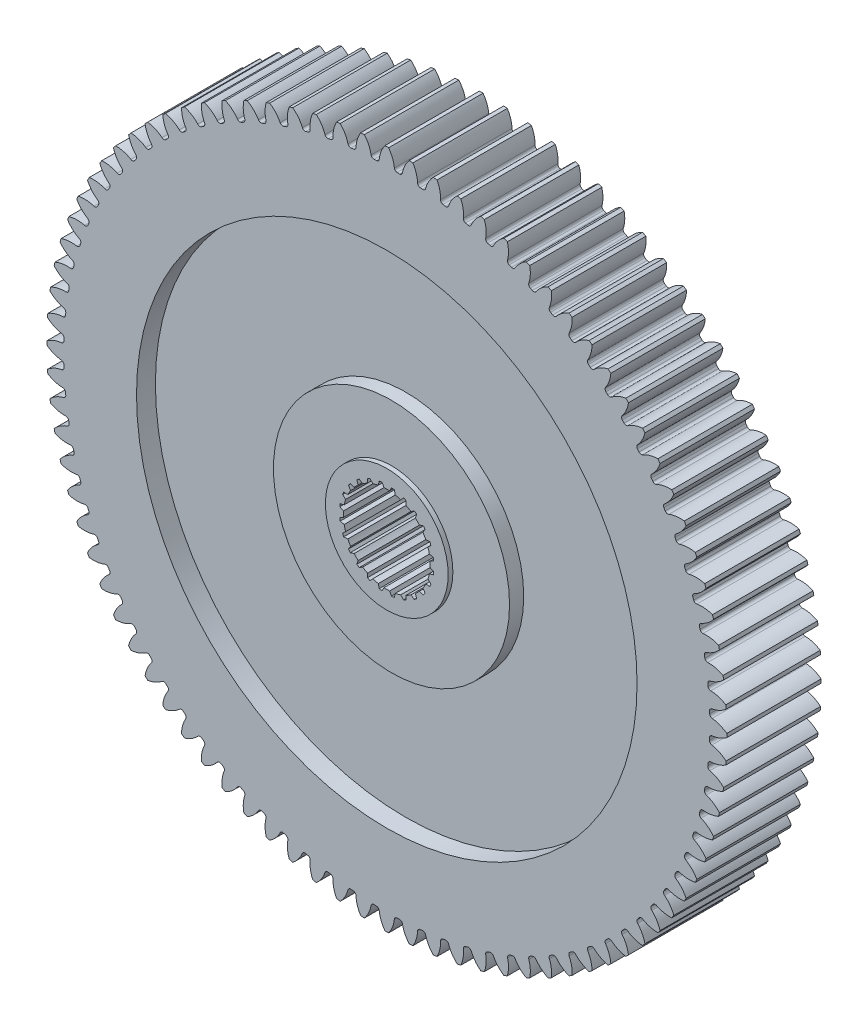
SolidWorks part; units mm, degrees
material "Acier allié"
ref_plane "Plan de face" through (0, 0, 0) normal (0, 0, 1) x (1, 0, 0)
ref_plane "Plan de dessus" through (0, 0, 0) normal (0, 1, 0) x (1, 0, 0)
ref_plane "Plan de droite" through (0, 0, 0) normal (1, 0, 0) x (0, 0, -1)
ref_axis "Axe roue" through (0, 0, 0) along (0, 0, 1)
sketch "Esquisse1" plane through (0, 0, 0) normal (1, 0, 0) x (0, 0, -1)
  line L0 (-15.5122, 0) -> (15.5122, 0) construction
  line L1 (0, 0) -> (0, 36) construction
  line L2 (-5, 4.6) -> (5, 4.6)
  line L3 (-5, 4.6) -> (-5, 6.5)
  line L4 (-5, 36) -> (5, 36)
  line L5 (5, 4.6) -> (5, 6.5)
  line L6 (-5, 26.5) -> (-3, 26.5)
  line L7 (-3, 26.5) -> (-3, 12.5)
  line L8 (-4.5, 6.5) -> (-5, 6.5)
  line L9 (-5, 26.5) -> (-5, 36)
  line L10 (4.5, 6.5) -> (5, 6.5)
  line L11 (3, 26.5) -> (3, 12.5)
  line L12 (5, 26.5) -> (3, 26.5)
  line L13 (5, 26.5) -> (5, 36)
  line L14 (4.5, 6.5) -> (4.5, 12.5)
  line L15 (4.5, 12.5) -> (3, 12.5)
  line L16 (-3, 12.5) -> (-4.5, 12.5)
  line L17 (-4.5, 12.5) -> (-4.5, 6.5)
  dimension "D1" = 9.2
  dimension "D2" = 72
  dimension "D3" = 10
  dimension "D4" = 2
  dimension "D5" = 53
  dimension "D6" = 13
  dimension "D7" = 25
  dimension "D8" = 1.5
revolve "Révolution1" add sketch "Esquisse1" angle 360 about L0
sketch "Esquisse2" plane through (0, 0, 0) normal (0, 0, 1) x (1, 0, 0)
  line L2 (0, -5.5) -> (0, 5.5) construction
  line L4 (0.25, 4.4931) -> (0.5, 4.9749)
  line L6 (0, 0) -> (0, 5.7732) construction
  line L7 (0, 0) -> (0.8204, 6.2318) construction
  line L8 (0.9214, 4.4047) -> (0.8046, 4.9348)
  arc A4 (0.9214, 4.4047) -> (0.25, 4.4931) centre (0, 0) ccw
  arc A5 (0.8046, 4.9348) -> (0.5, 4.9749) centre (0, 0) ccw
  dimension "D1" = 9
  dimension "D5" = 10
  dimension "D2" = 7.5
  dimension "D3" = 0.5
  dimension "D4" = 1
extrude "Enlèv. mat.-Extru.1" cut sketch "Esquisse2" against normal through all and the other way through all
pattern_circular "Répétition circulaire1" count 24 over 360 about axis through (0, 0, 0) along (0, 0, 1) of "Enlèv. mat.-Extru.1"
sketch "Esquisse3" plane through (0, 0, 0) normal (0, 0, 1) x (1, 0, 0)
  line L0 (0, 0) -> (0, 36) construction
  line L1 (0, 0) -> (2.5682, 35.9083) construction
  line L2 (0, 0) -> (1.2849, 35.9771) construction
  line L3 (0.6283, 35.1944) -> (0.3356, 35.9984) construction
  arc A0 (1.3506, 34.1733) -> (1.0907, 34.1826) centre (0, 0) ccw
  arc A1 (0.1965, 35.9995) -> (0.8021, 34.4497) centre (-2.3787, 34.0999) cw
  circle A2 centre (0, 0) radius 35.2 construction
  arc A3 (0.1965, 35.9995) -> (2.3722, 35.9218) centre (0, 0) cw
  circle A4 centre (0, 0) radius 36 construction
  circle A5 centre (0.6283, 35.1944) radius 0.6283 construction
  arc A6 (0.8021, 34.4497) -> (1.0907, 34.1826) centre (1.1003, 34.4824) ccw
  arc A7 (1.6576, 34.4191) -> (1.3506, 34.1733) centre (1.3625, 34.4731) cw
  arc A8 (2.3722, 35.9218) -> (1.6576, 34.4191) centre (4.8053, 33.8433) ccw
  point P9 (0.6283, 35.1944)
  dimension "D2" = 68.4
  dimension "D3" = 70.4
  dimension "D4" = 0.3
  dimension "D6" = 3.2
  dimension "D1" = 4.091
  dimension "D5" = 20
extrude "Enlèv. mat.-Extru.2" cut sketch "Esquisse3" against normal through all and the other way through all
pattern_circular "Répétition circulaire2" count 88 over 360 about axis through (0, 0, 0) along (0, 0, 1) of "Enlèv. mat.-Extru.2"
